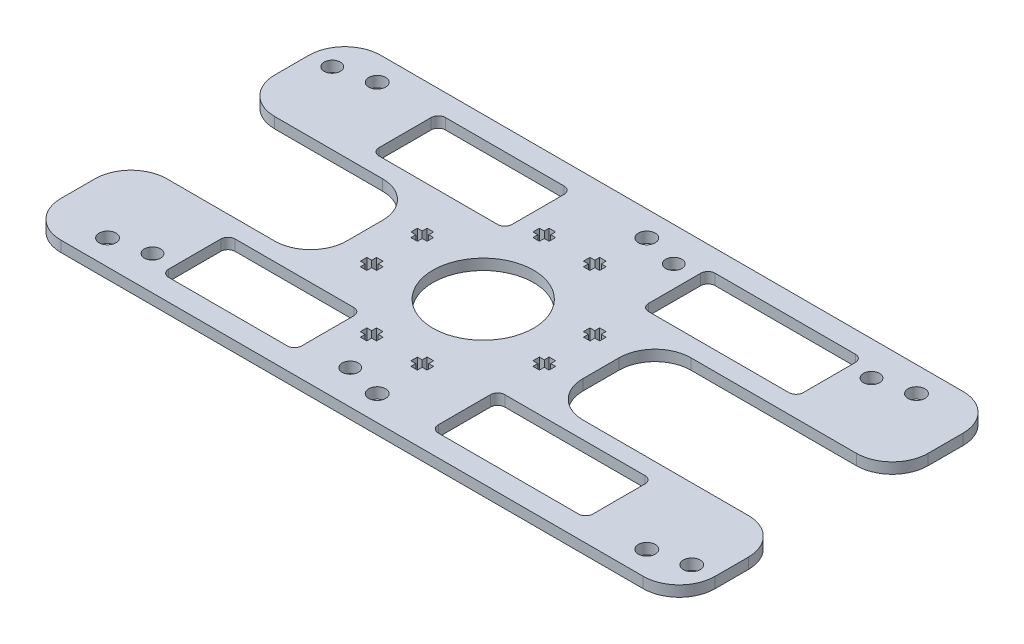
SolidWorks part; units mm, degrees
ref_plane "Front Plane" through (0, 0, 0) normal (0, 0, 1) x (1, 0, 0)
ref_plane "Top Plane" through (0, 0, 0) normal (0, 1, 0) x (1, 0, 0)
ref_plane "Right Plane" through (0, 0, 0) normal (1, 0, 0) x (0, 0, -1)
sketch "Sketch1" plane through (0, 0, 0) normal (0, 1, 0) x (1, 0, 0)
  line L2 (24.6852, -44.2664) -> (93.3361, -44.2664)
  line L4 (93.3361, 44.7336) -> (24.6837, 44.7336)
  line L7 (24.6837, 44.7336) -> (-88.6639, 44.7336)
  line L8 (-88.6639, 44.7336) -> (-88.6639, 15.2336)
  line L9 (-88.6639, -44.2664) -> (24.6852, -44.2664)
  line L17 (93.3361, -44.2664) -> (93.3361, -15)
  line L18 (-88.6639, 15.2336) -> (-38.6639, 15.2336)
  line L19 (-38.6639, 15.2336) -> (-38.6639, -14.7664)
  line L20 (-38.6639, -14.7664) -> (-88.6639, -14.7664)
  line L23 (93.3361, 15) -> (27.3361, 15)
  line L24 (27.3361, 15) -> (27.3361, -15)
  line L25 (27.3361, -15) -> (93.3361, -15)
  line L26 (-88.6639, -14.7664) -> (-88.6639, -44.2664)
  line L27 (93.3361, 15) -> (93.3361, 44.7336)
  circle A10 centre (-5.6639, 0.2336) radius 14
  circle A19 centre (-72.6639, -37.2664) radius 2.35
  circle A22 centre (2.3361, -37.2664) radius 2.35
  circle A25 centre (77.3361, -37.2664) radius 2.35
  circle A28 centre (77.3361, 37.7336) radius 2.35
  circle A31 centre (2.3361, 37.7336) radius 2.35
  circle A34 centre (-72.6639, 37.7336) radius 2.35
  point P7 (27.3361, 0)
  point P10 (-38.6639, 0.2336)
  dimension "D2" = 89
  dimension "D3" = 30
  dimension "D5" = 4.7
  dimension "D4" = 50
  dimension "D6" = 89
  dimension "D7" = 7
  dimension "D8" = 7
  dimension "D9" = 7
  dimension "D10" = 75
  dimension "D11" = 75
  dimension "D12" = 37.5
  dimension "D13" = 8
  dimension "D14" = 33
  dimension "D15" = 182
extrude "Boss-Extrude1" add sketch "Sketch1" along normal blind 3
sketch "Sketch2" plane through (0, 0, 0) normal (0, 1, 0) x (1, 0, 0)
  line L0 (0, 0) -> (-142.7211, 0) construction
ref_axis "Axis1" through (-5.6639, 0, -0.2336) along (0, 1, 0)
sketch "Sketch3" plane through (0, 3, 0) normal (0, 1, 0) x (1, 0, 0)
  line L12 (20.5861, -7.6958) -> (20.5861, -5.8958)
  line L13 (20.5861, -5.8958) -> (19.2361, -5.8958)
  line L14 (19.2361, -5.8958) -> (19.2361, -4.5458)
  line L15 (19.2361, -4.5458) -> (17.4361, -4.5458)
  line L16 (17.4361, -4.5458) -> (17.4361, -5.8958)
  line L17 (17.4361, -5.8958) -> (16.0861, -5.8958)
  line L18 (16.0861, -5.8958) -> (16.0861, -7.6958)
  line L19 (16.0861, -7.6958) -> (17.4361, -7.6958)
  line L20 (17.4361, -7.6958) -> (17.4361, -9.0458)
  line L21 (17.4361, -9.0458) -> (19.2361, -9.0458)
  line L22 (19.2361, -9.0458) -> (19.2361, -7.6958)
  line L23 (19.2361, -7.6958) -> (20.5861, -7.6958)
  line L24 (20.5861, -7.6958) -> (20.5861, -5.8958)
  line L25 (20.5861, -5.8958) -> (19.2361, -5.8958)
  line L26 (19.2361, -5.8958) -> (19.2361, -4.5458)
  line L27 (19.2361, -4.5458) -> (17.4361, -4.5458)
  line L28 (17.4361, -4.5458) -> (17.4361, -5.8958)
  line L29 (17.4361, -5.8958) -> (16.0861, -5.8958)
  line L30 (16.0861, -5.8958) -> (16.0861, -7.6958)
  line L31 (16.0861, -7.6958) -> (17.4361, -7.6958)
  line L32 (17.4361, -7.6958) -> (17.4361, -9.0458)
  line L33 (17.4361, -9.0458) -> (19.2361, -9.0458)
  line L34 (19.2361, -9.0458) -> (19.2361, -7.6958)
  line L35 (19.2361, -7.6958) -> (20.5861, -7.6958)
  line L36 (17.4361, 5.013) -> (19.2361, 5.013)
  line L37 (19.2361, 5.013) -> (19.2361, 6.363)
  line L38 (19.2361, 6.363) -> (20.5861, 6.363)
  line L39 (20.5861, 6.363) -> (20.5861, 8.163)
  line L40 (20.5861, 8.163) -> (19.2361, 8.163)
  line L41 (19.2361, 8.163) -> (19.2361, 9.513)
  line L42 (19.2361, 9.513) -> (17.4361, 9.513)
  line L43 (17.4361, 9.513) -> (17.4361, 8.163)
  line L44 (17.4361, 8.163) -> (16.0861, 8.163)
  line L45 (16.0861, 8.163) -> (16.0861, 6.363)
  line L46 (16.0861, 6.363) -> (17.4361, 6.363)
  line L47 (17.4361, 6.363) -> (17.4361, 5.013)
  line L48 (17.4361, 5.013) -> (19.2361, 5.013)
  line L49 (19.2361, 5.013) -> (19.2361, 6.363)
  line L50 (19.2361, 6.363) -> (20.5861, 6.363)
  line L51 (20.5861, 6.363) -> (20.5861, 8.163)
  line L52 (20.5861, 8.163) -> (19.2361, 8.163)
  line L53 (19.2361, 8.163) -> (19.2361, 9.513)
  line L54 (19.2361, 9.513) -> (17.4361, 9.513)
  line L55 (17.4361, 9.513) -> (17.4361, 8.163)
  line L56 (17.4361, 8.163) -> (16.0861, 8.163)
  line L57 (16.0861, 8.163) -> (16.0861, 6.363)
  line L58 (16.0861, 6.363) -> (17.4361, 6.363)
  line L59 (17.4361, 6.363) -> (17.4361, 5.013)
  line L60 (-13.5934, -22.8664) -> (-14.9434, -22.8664)
  line L61 (-14.9434, -22.8664) -> (-14.9434, -24.6664)
  line L62 (-14.9434, -24.6664) -> (-13.5934, -24.6664)
  line L63 (-13.5934, -24.6664) -> (-13.5934, -26.0164)
  line L64 (-13.5934, -26.0164) -> (-11.7934, -26.0164)
  line L65 (-11.7934, -26.0164) -> (-11.7934, -24.6664)
  line L66 (-11.7934, -24.6664) -> (-10.4434, -24.6664)
  line L67 (-10.4434, -24.6664) -> (-10.4434, -22.8664)
  line L68 (-10.4434, -22.8664) -> (-11.7934, -22.8664)
  line L69 (-11.7934, -22.8664) -> (-11.7934, -21.5164)
  line L70 (-11.7934, -21.5164) -> (-13.5934, -21.5164)
  line L71 (-13.5934, -21.5164) -> (-13.5934, -22.8664)
  line L72 (-13.5934, -22.8664) -> (-14.9434, -22.8664)
  line L73 (-14.9434, -22.8664) -> (-14.9434, -24.6664)
  line L74 (-14.9434, -24.6664) -> (-13.5934, -24.6664)
  line L75 (-13.5934, -24.6664) -> (-13.5934, -26.0164)
  line L76 (-13.5934, -26.0164) -> (-11.7934, -26.0164)
  line L77 (-11.7934, -26.0164) -> (-11.7934, -24.6664)
  line L78 (-11.7934, -24.6664) -> (-10.4434, -24.6664)
  line L79 (-10.4434, -24.6664) -> (-10.4434, -22.8664)
  line L80 (-10.4434, -22.8664) -> (-11.7934, -22.8664)
  line L81 (-11.7934, -22.8664) -> (-11.7934, -21.5164)
  line L82 (-11.7934, -21.5164) -> (-13.5934, -21.5164)
  line L83 (-13.5934, -21.5164) -> (-13.5934, -22.8664)
  line L84 (-31.9139, 8.163) -> (-31.9139, 6.363)
  line L85 (-31.9139, 6.363) -> (-30.5639, 6.363)
  line L86 (-30.5639, 6.363) -> (-30.5639, 5.013)
  line L87 (-30.5639, 5.013) -> (-28.7639, 5.013)
  line L88 (-28.7639, 5.013) -> (-28.7639, 6.363)
  line L89 (-28.7639, 6.363) -> (-27.4139, 6.363)
  line L90 (-27.4139, 6.363) -> (-27.4139, 8.163)
  line L91 (-27.4139, 8.163) -> (-28.7639, 8.163)
  line L92 (-28.7639, 8.163) -> (-28.7639, 9.513)
  line L93 (-28.7639, 9.513) -> (-30.5639, 9.513)
  line L94 (-30.5639, 9.513) -> (-30.5639, 8.163)
  line L95 (-30.5639, 8.163) -> (-31.9139, 8.163)
  line L96 (-31.9139, 8.163) -> (-31.9139, 6.363)
  line L97 (-31.9139, 6.363) -> (-30.5639, 6.363)
  line L98 (-30.5639, 6.363) -> (-30.5639, 5.013)
  line L99 (-30.5639, 5.013) -> (-28.7639, 5.013)
  line L100 (-28.7639, 5.013) -> (-28.7639, 6.363)
  line L101 (-28.7639, 6.363) -> (-27.4139, 6.363)
  line L102 (-27.4139, 6.363) -> (-27.4139, 8.163)
  line L103 (-27.4139, 8.163) -> (-28.7639, 8.163)
  line L104 (-28.7639, 8.163) -> (-28.7639, 9.513)
  line L105 (-28.7639, 9.513) -> (-30.5639, 9.513)
  line L106 (-30.5639, 9.513) -> (-30.5639, 8.163)
  line L107 (-30.5639, 8.163) -> (-31.9139, 8.163)
  line L108 (-0.8845, -24.6664) -> (0.4655, -24.6664)
  line L109 (0.4655, -24.6664) -> (0.4655, -26.0164)
  line L110 (0.4655, -26.0164) -> (2.2655, -26.0164)
  line L111 (2.2655, -26.0164) -> (2.2655, -24.6664)
  line L112 (2.2655, -24.6664) -> (3.6155, -24.6664)
  line L113 (3.6155, -24.6664) -> (3.6155, -22.8664)
  line L114 (3.6155, -22.8664) -> (2.2655, -22.8664)
  line L115 (2.2655, -22.8664) -> (2.2655, -21.5164)
  line L116 (2.2655, -21.5164) -> (0.4655, -21.5164)
  line L117 (0.4655, -21.5164) -> (0.4655, -22.8664)
  line L118 (0.4655, -22.8664) -> (-0.8845, -22.8664)
  line L119 (-0.8845, -22.8664) -> (-0.8845, -24.6664)
  line L120 (-0.8845, -24.6664) -> (0.4655, -24.6664)
  line L121 (0.4655, -24.6664) -> (0.4655, -26.0164)
  line L122 (0.4655, -26.0164) -> (2.2655, -26.0164)
  line L123 (2.2655, -26.0164) -> (2.2655, -24.6664)
  line L124 (2.2655, -24.6664) -> (3.6155, -24.6664)
  line L125 (3.6155, -24.6664) -> (3.6155, -22.8664)
  line L126 (3.6155, -22.8664) -> (2.2655, -22.8664)
  line L127 (2.2655, -22.8664) -> (2.2655, -21.5164)
  line L128 (2.2655, -21.5164) -> (0.4655, -21.5164)
  line L129 (0.4655, -21.5164) -> (0.4655, -22.8664)
  line L130 (0.4655, -22.8664) -> (-0.8845, -22.8664)
  line L131 (-0.8845, -22.8664) -> (-0.8845, -24.6664)
  line L132 (-31.9139, -7.6958) -> (-30.5639, -7.6958)
  line L133 (-31.9139, -5.8958) -> (-31.9139, -7.6958)
  line L134 (-30.5639, -5.8958) -> (-31.9139, -5.8958)
  line L135 (-30.5639, -4.5458) -> (-30.5639, -5.8958)
  line L136 (-28.7639, -4.5458) -> (-30.5639, -4.5458)
  line L137 (-28.7639, -5.8958) -> (-28.7639, -4.5458)
  line L138 (-27.4139, -5.8958) -> (-28.7639, -5.8958)
  line L139 (-27.4139, -7.6958) -> (-27.4139, -5.8958)
  line L140 (-28.7639, -7.6958) -> (-27.4139, -7.6958)
  line L141 (-28.7639, -9.0458) -> (-28.7639, -7.6958)
  line L142 (-30.5639, -9.0458) -> (-28.7639, -9.0458)
  line L143 (-30.5639, -7.6958) -> (-30.5639, -9.0458)
  line L144 (-31.9139, -7.6958) -> (-30.5639, -7.6958)
  line L145 (-31.9139, -5.8958) -> (-31.9139, -7.6958)
  line L146 (-30.5639, -5.8958) -> (-31.9139, -5.8958)
  line L147 (-30.5639, -4.5458) -> (-30.5639, -5.8958)
  line L148 (-28.7639, -4.5458) -> (-30.5639, -4.5458)
  line L149 (-28.7639, -5.8958) -> (-28.7639, -4.5458)
  line L150 (-27.4139, -5.8958) -> (-28.7639, -5.8958)
  line L151 (-27.4139, -7.6958) -> (-27.4139, -5.8958)
  line L152 (-28.7639, -7.6958) -> (-27.4139, -7.6958)
  line L153 (-28.7639, -9.0458) -> (-28.7639, -7.6958)
  line L154 (-30.5639, -9.0458) -> (-28.7639, -9.0458)
  line L155 (-30.5639, -7.6958) -> (-30.5639, -9.0458)
  line L156 (0.4655, 26.4836) -> (0.4655, 25.1336)
  line L157 (0.4655, 25.1336) -> (-0.8845, 25.1336)
  line L158 (-0.8845, 25.1336) -> (-0.8845, 23.3336)
  line L159 (-0.8845, 23.3336) -> (0.4655, 23.3336)
  line L160 (0.4655, 23.3336) -> (0.4655, 21.9836)
  line L161 (0.4655, 21.9836) -> (2.2655, 21.9836)
  line L162 (2.2655, 21.9836) -> (2.2655, 23.3336)
  line L163 (2.2655, 23.3336) -> (3.6155, 23.3336)
  line L164 (3.6155, 23.3336) -> (3.6155, 25.1336)
  line L165 (3.6155, 25.1336) -> (2.2655, 25.1336)
  line L166 (2.2655, 25.1336) -> (2.2655, 26.4836)
  line L167 (2.2655, 26.4836) -> (0.4655, 26.4836)
  line L168 (0.4655, 26.4836) -> (0.4655, 25.1336)
  line L169 (0.4655, 25.1336) -> (-0.8845, 25.1336)
  line L170 (-0.8845, 25.1336) -> (-0.8845, 23.3336)
  line L171 (-0.8845, 23.3336) -> (0.4655, 23.3336)
  line L172 (0.4655, 23.3336) -> (0.4655, 21.9836)
  line L173 (0.4655, 21.9836) -> (2.2655, 21.9836)
  line L174 (2.2655, 21.9836) -> (2.2655, 23.3336)
  line L175 (2.2655, 23.3336) -> (3.6155, 23.3336)
  line L176 (3.6155, 23.3336) -> (3.6155, 25.1336)
  line L177 (3.6155, 25.1336) -> (2.2655, 25.1336)
  line L178 (2.2655, 25.1336) -> (2.2655, 26.4836)
  line L179 (2.2655, 26.4836) -> (0.4655, 26.4836)
  line L180 (-13.5934, 26.4836) -> (-13.5934, 25.1336)
  line L181 (-13.5934, 25.1336) -> (-14.9434, 25.1336)
  line L182 (-14.9434, 25.1336) -> (-14.9434, 23.3336)
  line L183 (-14.9434, 23.3336) -> (-13.5934, 23.3336)
  line L184 (-13.5934, 23.3336) -> (-13.5934, 21.9836)
  line L185 (-13.5934, 21.9836) -> (-11.7934, 21.9836)
  line L186 (-11.7934, 21.9836) -> (-11.7934, 23.3336)
  line L187 (-11.7934, 23.3336) -> (-10.4434, 23.3336)
  line L188 (-10.4434, 23.3336) -> (-10.4434, 25.1336)
  line L189 (-10.4434, 25.1336) -> (-11.7934, 25.1336)
  line L190 (-11.7934, 25.1336) -> (-11.7934, 26.4836)
  line L191 (-11.7934, 26.4836) -> (-13.5934, 26.4836)
  line L192 (-13.5934, 26.4836) -> (-13.5934, 25.1336)
  line L193 (-13.5934, 25.1336) -> (-14.9434, 25.1336)
  line L194 (-14.9434, 25.1336) -> (-14.9434, 23.3336)
  line L195 (-14.9434, 23.3336) -> (-13.5934, 23.3336)
  line L196 (-13.5934, 23.3336) -> (-13.5934, 21.9836)
  line L197 (-13.5934, 21.9836) -> (-11.7934, 21.9836)
  line L198 (-11.7934, 21.9836) -> (-11.7934, 23.3336)
  line L199 (-11.7934, 23.3336) -> (-10.4434, 23.3336)
  line L200 (-10.4434, 23.3336) -> (-10.4434, 25.1336)
  line L201 (-10.4434, 25.1336) -> (-11.7934, 25.1336)
  line L202 (-11.7934, 25.1336) -> (-11.7934, 26.4836)
  line L203 (-11.7934, 26.4836) -> (-13.5934, 26.4836)
  dimension "D1" = 0
  dimension "D2" = 0
  dimension "D3" = 0
  dimension "D4" = 0
  dimension "D5" = 0
  dimension "D6" = 0
  dimension "D7" = 0
  dimension "D8" = 0
extrude "Cut-Extrude1" cut sketch "Sketch3" against normal through all
fillet "Fillet1" radius 10 12 edges at (27.3361, 1.5, 15) (27.3361, 1.5, -15) (93.3361, 1.5, 44.2664) (93.3361, 1.5, 15) (93.3361, 1.5, -15) (93.3361, 1.5, -44.7336) (-88.6639, 1.5, 44.2664) (-88.6639, 1.5, 14.7664) (-38.6639, 1.5, 14.7664) (-38.6639, 1.5, -15.2336) (-88.6639, 1.5, -15.2336) (-88.6639, 1.5, -44.7336)
sketch "Sketch4" plane through (0, 3, 0) normal (0, 1, 0) x (1, 0, 0)
  circle A0 centre (87.3361, -34.7664) radius 2.35 construction
  circle A1 centre (87.3361, -34.7664) radius 2.35
  circle A2 centre (67.3361, 35.2336) radius 2.25 construction
  circle A3 centre (67.3361, 35.2336) radius 2.25
  circle A4 centre (12.3361, 35.2336) radius 2.25 construction
  circle A5 centre (12.3361, 35.2336) radius 2.25
  circle A6 centre (-82.6639, 35.2336) radius 2.25 construction
  circle A7 centre (-82.6639, 35.2336) radius 2.25
  circle A8 centre (-62.6639, -34.7664) radius 2.25 construction
  circle A9 centre (-62.6639, -34.7664) radius 2.25
  circle A10 centre (-7.6639, -34.7664) radius 2.25 construction
  circle A11 centre (-7.6639, -34.7664) radius 2.25
extrude "Cut-Extrude2" cut sketch "Sketch4" against normal blind 10
sketch "Sketch5" plane through (0, 3, 0) normal (0, 1, 0) x (1, 0, 0)
  line L4 (59.3361, -19.7664) -> (20.3361, -19.7664)
  line L5 (61.3361, -36.2664) -> (61.3361, -21.7664)
  line L6 (20.3361, -38.2664) -> (59.3361, -38.2664)
  line L7 (18.3361, -21.7664) -> (18.3361, -36.2664)
  line L8 (59.3361, -19.7664) -> (20.3361, -19.7664)
  line L9 (61.3361, -36.2664) -> (61.3361, -21.7664)
  line L10 (20.3361, -38.2664) -> (59.3361, -38.2664)
  line L11 (18.3361, -21.7664) -> (18.3361, -36.2664)
  line L12 (18.3361, 36.7336) -> (18.3361, 22.2336)
  line L13 (59.3361, 38.7336) -> (20.3361, 38.7336)
  line L14 (61.3361, 22.2336) -> (61.3361, 36.7336)
  line L15 (20.3361, 20.2336) -> (59.3361, 20.2336)
  line L16 (18.3361, 36.7336) -> (18.3361, 22.2336)
  line L17 (59.3361, 38.7336) -> (20.3361, 38.7336)
  line L18 (61.3361, 22.2336) -> (61.3361, 36.7336)
  line L19 (20.3361, 20.2336) -> (59.3361, 20.2336)
  line L20 (-56.6639, -21.7664) -> (-56.6639, -36.2664)
  line L21 (-21.6639, -19.7664) -> (-54.6639, -19.7664)
  line L22 (-19.6639, -36.2664) -> (-19.6639, -21.7664)
  line L23 (-54.6639, -38.2664) -> (-21.6639, -38.2664)
  line L24 (-56.6639, -21.7664) -> (-56.6639, -36.2664)
  line L25 (-21.6639, -19.7664) -> (-54.6639, -19.7664)
  line L26 (-19.6639, -36.2664) -> (-19.6639, -21.7664)
  line L27 (-54.6639, -38.2664) -> (-21.6639, -38.2664)
  line L28 (-56.6639, 36.7336) -> (-56.6639, 22.2336)
  line L29 (-21.6639, 38.7336) -> (-54.6639, 38.7336)
  line L30 (-19.6639, 22.2336) -> (-19.6639, 36.7336)
  line L31 (-54.6639, 20.2336) -> (-21.6639, 20.2336)
  line L32 (-56.6639, 36.7336) -> (-56.6639, 22.2336)
  line L33 (-21.6639, 38.7336) -> (-54.6639, 38.7336)
  line L34 (-19.6639, 22.2336) -> (-19.6639, 36.7336)
  line L35 (-54.6639, 20.2336) -> (-21.6639, 20.2336)
  arc A4 (61.3361, -21.7664) -> (59.3361, -19.7664) centre (59.3361, -21.7664) ccw
  arc A5 (59.3361, -38.2664) -> (61.3361, -36.2664) centre (59.3361, -36.2664) ccw
  arc A6 (18.3361, -36.2664) -> (20.3361, -38.2664) centre (20.3361, -36.2664) ccw
  arc A7 (20.3361, -19.7664) -> (18.3361, -21.7664) centre (20.3361, -21.7664) ccw
  arc A8 (61.3361, -21.7664) -> (59.3361, -19.7664) centre (59.3361, -21.7664) ccw
  arc A9 (59.3361, -38.2664) -> (61.3361, -36.2664) centre (59.3361, -36.2664) ccw
  arc A10 (18.3361, -36.2664) -> (20.3361, -38.2664) centre (20.3361, -36.2664) ccw
  arc A11 (20.3361, -19.7664) -> (18.3361, -21.7664) centre (20.3361, -21.7664) ccw
  arc A12 (20.3361, 38.7336) -> (18.3361, 36.7336) centre (20.3361, 36.7336) ccw
  arc A13 (61.3361, 36.7336) -> (59.3361, 38.7336) centre (59.3361, 36.7336) ccw
  arc A14 (59.3361, 20.2336) -> (61.3361, 22.2336) centre (59.3361, 22.2336) ccw
  arc A15 (18.3361, 22.2336) -> (20.3361, 20.2336) centre (20.3361, 22.2336) ccw
  arc A16 (20.3361, 38.7336) -> (18.3361, 36.7336) centre (20.3361, 36.7336) ccw
  arc A17 (61.3361, 36.7336) -> (59.3361, 38.7336) centre (59.3361, 36.7336) ccw
  arc A18 (59.3361, 20.2336) -> (61.3361, 22.2336) centre (59.3361, 22.2336) ccw
  arc A19 (18.3361, 22.2336) -> (20.3361, 20.2336) centre (20.3361, 22.2336) ccw
  arc A20 (-54.6639, -19.7664) -> (-56.6639, -21.7664) centre (-54.6639, -21.7664) ccw
  arc A21 (-19.6639, -21.7664) -> (-21.6639, -19.7664) centre (-21.6639, -21.7664) ccw
  arc A22 (-21.6639, -38.2664) -> (-19.6639, -36.2664) centre (-21.6639, -36.2664) ccw
  arc A23 (-56.6639, -36.2664) -> (-54.6639, -38.2664) centre (-54.6639, -36.2664) ccw
  arc A24 (-54.6639, -19.7664) -> (-56.6639, -21.7664) centre (-54.6639, -21.7664) ccw
  arc A25 (-19.6639, -21.7664) -> (-21.6639, -19.7664) centre (-21.6639, -21.7664) ccw
  arc A26 (-21.6639, -38.2664) -> (-19.6639, -36.2664) centre (-21.6639, -36.2664) ccw
  arc A27 (-56.6639, -36.2664) -> (-54.6639, -38.2664) centre (-54.6639, -36.2664) ccw
  arc A28 (-54.6639, 38.7336) -> (-56.6639, 36.7336) centre (-54.6639, 36.7336) ccw
  arc A29 (-19.6639, 36.7336) -> (-21.6639, 38.7336) centre (-21.6639, 36.7336) ccw
  arc A30 (-21.6639, 20.2336) -> (-19.6639, 22.2336) centre (-21.6639, 22.2336) ccw
  arc A31 (-56.6639, 22.2336) -> (-54.6639, 20.2336) centre (-54.6639, 22.2336) ccw
  arc A32 (-54.6639, 38.7336) -> (-56.6639, 36.7336) centre (-54.6639, 36.7336) ccw
  arc A33 (-19.6639, 36.7336) -> (-21.6639, 38.7336) centre (-21.6639, 36.7336) ccw
  arc A34 (-21.6639, 20.2336) -> (-19.6639, 22.2336) centre (-21.6639, 22.2336) ccw
  arc A35 (-56.6639, 22.2336) -> (-54.6639, 20.2336) centre (-54.6639, 22.2336) ccw
  dimension "D1" = 0
  dimension "D2" = 0
  dimension "D3" = 0
  dimension "D4" = 0
extrude "Cut-Extrude3" cut sketch "Sketch5" against normal blind 10
sketch "Sketch6" plane through (0, 3, 0) normal (0, 1, 0) x (1, 0, 0)
  line L4 (-54.6639, 20.2336) -> (-21.6639, 20.2336)
  line L5 (-56.6639, 36.7336) -> (-56.6639, 22.2336)
  line L6 (-21.6639, 38.7336) -> (-54.6639, 38.7336)
  line L7 (-19.6639, 22.2336) -> (-19.6639, 36.7336)
  line L8 (-54.6639, 20.2336) -> (-21.6639, 20.2336)
  line L9 (-56.6639, 36.7336) -> (-56.6639, 22.2336)
  line L10 (-21.6639, 38.7336) -> (-54.6639, 38.7336)
  line L11 (-19.6639, 22.2336) -> (-19.6639, 36.7336)
  line L12 (20.3361, 20.2336) -> (59.3361, 20.2336)
  line L13 (18.3361, 36.7336) -> (18.3361, 22.2336)
  line L14 (59.3361, 38.7336) -> (20.3361, 38.7336)
  line L15 (61.3361, 22.2336) -> (61.3361, 36.7336)
  line L16 (20.3361, 20.2336) -> (59.3361, 20.2336)
  line L17 (18.3361, 36.7336) -> (18.3361, 22.2336)
  line L18 (59.3361, 38.7336) -> (20.3361, 38.7336)
  line L19 (61.3361, 22.2336) -> (61.3361, 36.7336)
  line L20 (-54.6639, -38.2664) -> (-21.6639, -38.2664)
  line L21 (-56.6639, -21.7664) -> (-56.6639, -36.2664)
  line L22 (-21.6639, -19.7664) -> (-54.6639, -19.7664)
  line L23 (-19.6639, -36.2664) -> (-19.6639, -21.7664)
  line L24 (-54.6639, -38.2664) -> (-21.6639, -38.2664)
  line L25 (-56.6639, -21.7664) -> (-56.6639, -36.2664)
  line L26 (-21.6639, -19.7664) -> (-54.6639, -19.7664)
  line L27 (-19.6639, -36.2664) -> (-19.6639, -21.7664)
  line L28 (18.3361, -21.7664) -> (18.3361, -36.2664)
  line L29 (59.3361, -19.7664) -> (20.3361, -19.7664)
  line L30 (61.3361, -36.2664) -> (61.3361, -21.7664)
  line L31 (20.3361, -38.2664) -> (59.3361, -38.2664)
  line L32 (18.3361, -21.7664) -> (18.3361, -36.2664)
  line L33 (59.3361, -19.7664) -> (20.3361, -19.7664)
  line L34 (61.3361, -36.2664) -> (61.3361, -21.7664)
  line L35 (20.3361, -38.2664) -> (59.3361, -38.2664)
  line L36 (20.5861, -7.6958) -> (20.5861, -5.8958)
  line L37 (19.2361, -7.6958) -> (20.5861, -7.6958)
  line L38 (19.2361, -9.0458) -> (19.2361, -7.6958)
  line L39 (17.4361, -9.0458) -> (19.2361, -9.0458)
  line L40 (17.4361, -7.6958) -> (17.4361, -9.0458)
  line L41 (16.0861, -7.6958) -> (17.4361, -7.6958)
  line L42 (16.0861, -5.8958) -> (16.0861, -7.6958)
  line L43 (17.4361, -5.8958) -> (16.0861, -5.8958)
  line L44 (17.4361, -4.5458) -> (17.4361, -5.8958)
  line L45 (19.2361, -4.5458) -> (17.4361, -4.5458)
  line L46 (19.2361, -5.8958) -> (19.2361, -4.5458)
  line L47 (20.5861, -5.8958) -> (19.2361, -5.8958)
  line L48 (20.5861, -7.6958) -> (20.5861, -5.8958)
  line L49 (19.2361, -7.6958) -> (20.5861, -7.6958)
  line L50 (19.2361, -9.0458) -> (19.2361, -7.6958)
  line L51 (17.4361, -9.0458) -> (19.2361, -9.0458)
  line L52 (17.4361, -7.6958) -> (17.4361, -9.0458)
  line L53 (16.0861, -7.6958) -> (17.4361, -7.6958)
  line L54 (16.0861, -5.8958) -> (16.0861, -7.6958)
  line L55 (17.4361, -5.8958) -> (16.0861, -5.8958)
  line L56 (17.4361, -4.5458) -> (17.4361, -5.8958)
  line L57 (19.2361, -4.5458) -> (17.4361, -4.5458)
  line L58 (19.2361, -5.8958) -> (19.2361, -4.5458)
  line L59 (20.5861, -5.8958) -> (19.2361, -5.8958)
  line L60 (-30.5639, -9.0458) -> (-28.7639, -9.0458)
  line L61 (-30.5639, -7.6958) -> (-30.5639, -9.0458)
  line L62 (-31.9139, -7.6958) -> (-30.5639, -7.6958)
  line L63 (-31.9139, -5.8958) -> (-31.9139, -7.6958)
  line L64 (-30.5639, -5.8958) -> (-31.9139, -5.8958)
  line L65 (-30.5639, -4.5458) -> (-30.5639, -5.8958)
  line L66 (-28.7639, -4.5458) -> (-30.5639, -4.5458)
  line L67 (-28.7639, -5.8958) -> (-28.7639, -4.5458)
  line L68 (-27.4139, -5.8958) -> (-28.7639, -5.8958)
  line L69 (-27.4139, -7.6958) -> (-27.4139, -5.8958)
  line L70 (-28.7639, -7.6958) -> (-27.4139, -7.6958)
  line L71 (-28.7639, -9.0458) -> (-28.7639, -7.6958)
  line L72 (-30.5639, -9.0458) -> (-28.7639, -9.0458)
  line L73 (-30.5639, -7.6958) -> (-30.5639, -9.0458)
  line L74 (-31.9139, -7.6958) -> (-30.5639, -7.6958)
  line L75 (-31.9139, -5.8958) -> (-31.9139, -7.6958)
  line L76 (-30.5639, -5.8958) -> (-31.9139, -5.8958)
  line L77 (-30.5639, -4.5458) -> (-30.5639, -5.8958)
  line L78 (-28.7639, -4.5458) -> (-30.5639, -4.5458)
  line L79 (-28.7639, -5.8958) -> (-28.7639, -4.5458)
  line L80 (-27.4139, -5.8958) -> (-28.7639, -5.8958)
  line L81 (-27.4139, -7.6958) -> (-27.4139, -5.8958)
  line L82 (-28.7639, -7.6958) -> (-27.4139, -7.6958)
  line L83 (-28.7639, -9.0458) -> (-28.7639, -7.6958)
  line L84 (0.4655, 26.4836) -> (0.4655, 25.1336)
  line L85 (2.2655, 26.4836) -> (0.4655, 26.4836)
  line L86 (2.2655, 25.1336) -> (2.2655, 26.4836)
  line L87 (3.6155, 25.1336) -> (2.2655, 25.1336)
  line L88 (3.6155, 23.3336) -> (3.6155, 25.1336)
  line L89 (2.2655, 23.3336) -> (3.6155, 23.3336)
  line L90 (2.2655, 21.9836) -> (2.2655, 23.3336)
  line L91 (0.4655, 21.9836) -> (2.2655, 21.9836)
  line L92 (0.4655, 23.3336) -> (0.4655, 21.9836)
  line L93 (-0.8845, 23.3336) -> (0.4655, 23.3336)
  line L94 (-0.8845, 25.1336) -> (-0.8845, 23.3336)
  line L95 (0.4655, 25.1336) -> (-0.8845, 25.1336)
  line L96 (0.4655, 26.4836) -> (0.4655, 25.1336)
  line L97 (2.2655, 26.4836) -> (0.4655, 26.4836)
  line L98 (2.2655, 25.1336) -> (2.2655, 26.4836)
  line L99 (3.6155, 25.1336) -> (2.2655, 25.1336)
  line L100 (3.6155, 23.3336) -> (3.6155, 25.1336)
  line L101 (2.2655, 23.3336) -> (3.6155, 23.3336)
  line L102 (2.2655, 21.9836) -> (2.2655, 23.3336)
  line L103 (0.4655, 21.9836) -> (2.2655, 21.9836)
  line L104 (0.4655, 23.3336) -> (0.4655, 21.9836)
  line L105 (-0.8845, 23.3336) -> (0.4655, 23.3336)
  line L106 (-0.8845, 25.1336) -> (-0.8845, 23.3336)
  line L107 (0.4655, 25.1336) -> (-0.8845, 25.1336)
  line L108 (-14.9434, 25.1336) -> (-14.9434, 23.3336)
  line L109 (-13.5934, 25.1336) -> (-14.9434, 25.1336)
  line L110 (-13.5934, 26.4836) -> (-13.5934, 25.1336)
  line L111 (-11.7934, 26.4836) -> (-13.5934, 26.4836)
  line L112 (-11.7934, 25.1336) -> (-11.7934, 26.4836)
  line L113 (-10.4434, 25.1336) -> (-11.7934, 25.1336)
  line L114 (-10.4434, 23.3336) -> (-10.4434, 25.1336)
  line L115 (-11.7934, 23.3336) -> (-10.4434, 23.3336)
  line L116 (-11.7934, 21.9836) -> (-11.7934, 23.3336)
  line L117 (-13.5934, 21.9836) -> (-11.7934, 21.9836)
  line L118 (-13.5934, 23.3336) -> (-13.5934, 21.9836)
  line L119 (-14.9434, 23.3336) -> (-13.5934, 23.3336)
  line L120 (-14.9434, 25.1336) -> (-14.9434, 23.3336)
  line L121 (-13.5934, 25.1336) -> (-14.9434, 25.1336)
  line L122 (-13.5934, 26.4836) -> (-13.5934, 25.1336)
  line L123 (-11.7934, 26.4836) -> (-13.5934, 26.4836)
  line L124 (-11.7934, 25.1336) -> (-11.7934, 26.4836)
  line L125 (-10.4434, 25.1336) -> (-11.7934, 25.1336)
  line L126 (-10.4434, 23.3336) -> (-10.4434, 25.1336)
  line L127 (-11.7934, 23.3336) -> (-10.4434, 23.3336)
  line L128 (-11.7934, 21.9836) -> (-11.7934, 23.3336)
  line L129 (-13.5934, 21.9836) -> (-11.7934, 21.9836)
  line L130 (-13.5934, 23.3336) -> (-13.5934, 21.9836)
  line L131 (-14.9434, 23.3336) -> (-13.5934, 23.3336)
  line L132 (19.2361, 6.363) -> (20.5861, 6.363)
  line L133 (19.2361, 5.013) -> (19.2361, 6.363)
  line L134 (17.4361, 5.013) -> (19.2361, 5.013)
  line L135 (17.4361, 6.363) -> (17.4361, 5.013)
  line L136 (16.0861, 6.363) -> (17.4361, 6.363)
  line L137 (16.0861, 8.163) -> (16.0861, 6.363)
  line L138 (17.4361, 8.163) -> (16.0861, 8.163)
  line L139 (17.4361, 9.513) -> (17.4361, 8.163)
  line L140 (19.2361, 9.513) -> (17.4361, 9.513)
  line L141 (19.2361, 8.163) -> (19.2361, 9.513)
  line L142 (20.5861, 8.163) -> (19.2361, 8.163)
  line L143 (20.5861, 6.363) -> (20.5861, 8.163)
  line L144 (19.2361, 6.363) -> (20.5861, 6.363)
  line L145 (19.2361, 5.013) -> (19.2361, 6.363)
  line L146 (17.4361, 5.013) -> (19.2361, 5.013)
  line L147 (17.4361, 6.363) -> (17.4361, 5.013)
  line L148 (16.0861, 6.363) -> (17.4361, 6.363)
  line L149 (16.0861, 8.163) -> (16.0861, 6.363)
  line L150 (17.4361, 8.163) -> (16.0861, 8.163)
  line L151 (17.4361, 9.513) -> (17.4361, 8.163)
  line L152 (19.2361, 9.513) -> (17.4361, 9.513)
  line L153 (19.2361, 8.163) -> (19.2361, 9.513)
  line L154 (20.5861, 8.163) -> (19.2361, 8.163)
  line L155 (20.5861, 6.363) -> (20.5861, 8.163)
  line L156 (-31.9139, 8.163) -> (-31.9139, 6.363)
  line L157 (-30.5639, 8.163) -> (-31.9139, 8.163)
  line L158 (-30.5639, 9.513) -> (-30.5639, 8.163)
  line L159 (-28.7639, 9.513) -> (-30.5639, 9.513)
  line L160 (-28.7639, 8.163) -> (-28.7639, 9.513)
  line L161 (-27.4139, 8.163) -> (-28.7639, 8.163)
  line L162 (-27.4139, 6.363) -> (-27.4139, 8.163)
  line L163 (-28.7639, 6.363) -> (-27.4139, 6.363)
  line L164 (-28.7639, 5.013) -> (-28.7639, 6.363)
  line L165 (-30.5639, 5.013) -> (-28.7639, 5.013)
  line L166 (-30.5639, 6.363) -> (-30.5639, 5.013)
  line L167 (-31.9139, 6.363) -> (-30.5639, 6.363)
  line L168 (-31.9139, 8.163) -> (-31.9139, 6.363)
  line L169 (-30.5639, 8.163) -> (-31.9139, 8.163)
  line L170 (-30.5639, 9.513) -> (-30.5639, 8.163)
  line L171 (-28.7639, 9.513) -> (-30.5639, 9.513)
  line L172 (-28.7639, 8.163) -> (-28.7639, 9.513)
  line L173 (-27.4139, 8.163) -> (-28.7639, 8.163)
  line L174 (-27.4139, 6.363) -> (-27.4139, 8.163)
  line L175 (-28.7639, 6.363) -> (-27.4139, 6.363)
  line L176 (-28.7639, 5.013) -> (-28.7639, 6.363)
  line L177 (-30.5639, 5.013) -> (-28.7639, 5.013)
  line L178 (-30.5639, 6.363) -> (-30.5639, 5.013)
  line L179 (-31.9139, 6.363) -> (-30.5639, 6.363)
  line L180 (0.4655, -26.0164) -> (2.2655, -26.0164)
  line L181 (0.4655, -24.6664) -> (0.4655, -26.0164)
  line L182 (-0.8845, -24.6664) -> (0.4655, -24.6664)
  line L183 (-0.8845, -22.8664) -> (-0.8845, -24.6664)
  line L184 (0.4655, -22.8664) -> (-0.8845, -22.8664)
  line L185 (0.4655, -21.5164) -> (0.4655, -22.8664)
  line L186 (2.2655, -21.5164) -> (0.4655, -21.5164)
  line L187 (2.2655, -22.8664) -> (2.2655, -21.5164)
  line L188 (3.6155, -22.8664) -> (2.2655, -22.8664)
  line L189 (3.6155, -24.6664) -> (3.6155, -22.8664)
  line L190 (2.2655, -24.6664) -> (3.6155, -24.6664)
  line L191 (2.2655, -26.0164) -> (2.2655, -24.6664)
  line L192 (0.4655, -26.0164) -> (2.2655, -26.0164)
  line L193 (0.4655, -24.6664) -> (0.4655, -26.0164)
  line L194 (-0.8845, -24.6664) -> (0.4655, -24.6664)
  line L195 (-0.8845, -22.8664) -> (-0.8845, -24.6664)
  line L196 (0.4655, -22.8664) -> (-0.8845, -22.8664)
  line L197 (0.4655, -21.5164) -> (0.4655, -22.8664)
  line L198 (2.2655, -21.5164) -> (0.4655, -21.5164)
  line L199 (2.2655, -22.8664) -> (2.2655, -21.5164)
  line L200 (3.6155, -22.8664) -> (2.2655, -22.8664)
  line L201 (3.6155, -24.6664) -> (3.6155, -22.8664)
  line L202 (2.2655, -24.6664) -> (3.6155, -24.6664)
  line L203 (2.2655, -26.0164) -> (2.2655, -24.6664)
  line L212 (-13.5934, -22.8664) -> (-14.9434, -22.8664)
  line L213 (-13.5934, -21.5164) -> (-13.5934, -22.8664)
  line L214 (-11.7934, -21.5164) -> (-13.5934, -21.5164)
  line L215 (-11.7934, -22.8664) -> (-11.7934, -21.5164)
  line L216 (-10.4434, -22.8664) -> (-11.7934, -22.8664)
  line L217 (-10.4434, -24.6664) -> (-10.4434, -22.8664)
  line L218 (-11.7934, -24.6664) -> (-10.4434, -24.6664)
  line L219 (-11.7934, -26.0164) -> (-11.7934, -24.6664)
  line L220 (-13.5934, -26.0164) -> (-11.7934, -26.0164)
  line L221 (-13.5934, -24.6664) -> (-13.5934, -26.0164)
  line L222 (-14.9434, -24.6664) -> (-13.5934, -24.6664)
  line L223 (-14.9434, -22.8664) -> (-14.9434, -24.6664)
  line L224 (-13.5934, -22.8664) -> (-14.9434, -22.8664)
  line L225 (-13.5934, -21.5164) -> (-13.5934, -22.8664)
  line L226 (-11.7934, -21.5164) -> (-13.5934, -21.5164)
  line L227 (-11.7934, -22.8664) -> (-11.7934, -21.5164)
  line L228 (-10.4434, -22.8664) -> (-11.7934, -22.8664)
  line L229 (-10.4434, -24.6664) -> (-10.4434, -22.8664)
  line L230 (-11.7934, -24.6664) -> (-10.4434, -24.6664)
  line L231 (-11.7934, -26.0164) -> (-11.7934, -24.6664)
  line L232 (-13.5934, -26.0164) -> (-11.7934, -26.0164)
  line L233 (-13.5934, -24.6664) -> (-13.5934, -26.0164)
  line L234 (-14.9434, -24.6664) -> (-13.5934, -24.6664)
  line L235 (-14.9434, -22.8664) -> (-14.9434, -24.6664)
  line L236 (-78.6639, -44.2664) -> (83.3361, -44.2664)
  line L237 (93.3361, -34.2664) -> (93.3361, -25)
  line L238 (83.3361, -15) -> (37.3361, -15)
  line L239 (27.3361, -5) -> (27.3361, 5)
  line L240 (37.3361, 15) -> (83.3361, 15)
  line L241 (93.3361, 25) -> (93.3361, 34.7336)
  line L242 (83.3361, 44.7336) -> (-78.6639, 44.7336)
  line L243 (-88.6639, 34.7336) -> (-88.6639, 25.2336)
  line L244 (-78.6639, 15.2336) -> (-48.6639, 15.2336)
  line L245 (-38.6639, 5.2336) -> (-38.6639, -4.7664)
  line L246 (-48.6639, -14.7664) -> (-78.6639, -14.7664)
  line L247 (-88.6639, -24.7664) -> (-88.6639, -34.2664)
  line L248 (-78.6639, -44.2664) -> (83.3361, -44.2664)
  line L249 (93.3361, -34.2664) -> (93.3361, -25)
  line L250 (83.3361, -15) -> (37.3361, -15)
  line L251 (27.3361, -5) -> (27.3361, 5)
  line L252 (37.3361, 15) -> (83.3361, 15)
  line L253 (93.3361, 25) -> (93.3361, 34.7336)
  line L254 (83.3361, 44.7336) -> (-78.6639, 44.7336)
  line L255 (-88.6639, 34.7336) -> (-88.6639, 25.2336)
  line L256 (-78.6639, 15.2336) -> (-48.6639, 15.2336)
  line L257 (-38.6639, 5.2336) -> (-38.6639, -4.7664)
  line L258 (-48.6639, -14.7664) -> (-78.6639, -14.7664)
  line L259 (-88.6639, -24.7664) -> (-88.6639, -34.2664)
  circle A0 centre (77.3361, 37.7336) radius 2.35 construction
  circle A1 centre (-72.6639, -37.2664) radius 2.35
  circle A2 centre (-72.6639, -37.2664) radius 2.35
  circle A3 centre (2.3361, -37.2664) radius 2.35
  arc A4 (-56.6639, 22.2336) -> (-54.6639, 20.2336) centre (-54.6639, 22.2336) ccw
  arc A5 (-54.6639, 38.7336) -> (-56.6639, 36.7336) centre (-54.6639, 36.7336) ccw
  arc A6 (-19.6639, 36.7336) -> (-21.6639, 38.7336) centre (-21.6639, 36.7336) ccw
  arc A7 (-21.6639, 20.2336) -> (-19.6639, 22.2336) centre (-21.6639, 22.2336) ccw
  arc A8 (-56.6639, 22.2336) -> (-54.6639, 20.2336) centre (-54.6639, 22.2336) ccw
  arc A9 (-54.6639, 38.7336) -> (-56.6639, 36.7336) centre (-54.6639, 36.7336) ccw
  arc A10 (-19.6639, 36.7336) -> (-21.6639, 38.7336) centre (-21.6639, 36.7336) ccw
  arc A11 (-21.6639, 20.2336) -> (-19.6639, 22.2336) centre (-21.6639, 22.2336) ccw
  arc A12 (18.3361, 22.2336) -> (20.3361, 20.2336) centre (20.3361, 22.2336) ccw
  arc A13 (20.3361, 38.7336) -> (18.3361, 36.7336) centre (20.3361, 36.7336) ccw
  arc A14 (61.3361, 36.7336) -> (59.3361, 38.7336) centre (59.3361, 36.7336) ccw
  arc A15 (59.3361, 20.2336) -> (61.3361, 22.2336) centre (59.3361, 22.2336) ccw
  arc A16 (18.3361, 22.2336) -> (20.3361, 20.2336) centre (20.3361, 22.2336) ccw
  arc A17 (20.3361, 38.7336) -> (18.3361, 36.7336) centre (20.3361, 36.7336) ccw
  arc A18 (61.3361, 36.7336) -> (59.3361, 38.7336) centre (59.3361, 36.7336) ccw
  arc A19 (59.3361, 20.2336) -> (61.3361, 22.2336) centre (59.3361, 22.2336) ccw
  circle A20 centre (2.3361, -37.2664) radius 2.35
  circle A21 centre (77.3361, -37.2664) radius 2.35
  circle A22 centre (77.3361, -37.2664) radius 2.35
  circle A23 centre (2.3361, 37.7336) radius 2.35
  circle A24 centre (2.3361, 37.7336) radius 2.35
  circle A25 centre (-72.6639, 37.7336) radius 2.35
  circle A26 centre (-72.6639, 37.7336) radius 2.35
  circle A27 centre (12.3361, 35.2336) radius 2.25
  circle A28 centre (12.3361, 35.2336) radius 2.25
  circle A29 centre (-82.6639, 35.2336) radius 2.25
  arc A30 (-56.6639, -36.2664) -> (-54.6639, -38.2664) centre (-54.6639, -36.2664) ccw
  arc A31 (-54.6639, -19.7664) -> (-56.6639, -21.7664) centre (-54.6639, -21.7664) ccw
  arc A32 (-19.6639, -21.7664) -> (-21.6639, -19.7664) centre (-21.6639, -21.7664) ccw
  arc A33 (-21.6639, -38.2664) -> (-19.6639, -36.2664) centre (-21.6639, -36.2664) ccw
  arc A34 (-56.6639, -36.2664) -> (-54.6639, -38.2664) centre (-54.6639, -36.2664) ccw
  arc A35 (-54.6639, -19.7664) -> (-56.6639, -21.7664) centre (-54.6639, -21.7664) ccw
  arc A36 (-19.6639, -21.7664) -> (-21.6639, -19.7664) centre (-21.6639, -21.7664) ccw
  arc A37 (-21.6639, -38.2664) -> (-19.6639, -36.2664) centre (-21.6639, -36.2664) ccw
  circle A38 centre (-82.6639, 35.2336) radius 2.25
  circle A39 centre (-62.6639, -34.7664) radius 2.25
  circle A40 centre (-62.6639, -34.7664) radius 2.25
  circle A41 centre (-7.6639, -34.7664) radius 2.25
  circle A42 centre (-7.6639, -34.7664) radius 2.25
  circle A43 centre (87.3361, -34.7664) radius 2.35
  circle A44 centre (87.3361, -34.7664) radius 2.35
  circle A45 centre (67.3361, 35.2336) radius 2.25 construction
  circle A46 centre (77.3361, 37.7336) radius 2.35
  circle A47 centre (67.3361, 35.2336) radius 2.25
  arc A48 (20.3361, -19.7664) -> (18.3361, -21.7664) centre (20.3361, -21.7664) ccw
  arc A49 (61.3361, -21.7664) -> (59.3361, -19.7664) centre (59.3361, -21.7664) ccw
  arc A50 (59.3361, -38.2664) -> (61.3361, -36.2664) centre (59.3361, -36.2664) ccw
  arc A51 (18.3361, -36.2664) -> (20.3361, -38.2664) centre (20.3361, -36.2664) ccw
  arc A52 (20.3361, -19.7664) -> (18.3361, -21.7664) centre (20.3361, -21.7664) ccw
  arc A53 (61.3361, -21.7664) -> (59.3361, -19.7664) centre (59.3361, -21.7664) ccw
  arc A54 (59.3361, -38.2664) -> (61.3361, -36.2664) centre (59.3361, -36.2664) ccw
  arc A55 (18.3361, -36.2664) -> (20.3361, -38.2664) centre (20.3361, -36.2664) ccw
  circle A56 centre (-5.6639, 0.2336) radius 14 construction
  circle A57 centre (-5.6639, 0.2336) radius 14
  arc A68 (83.3361, -44.2664) -> (93.3361, -34.2664) centre (83.3361, -34.2664) ccw
  arc A69 (93.3361, -25) -> (83.3361, -15) centre (83.3361, -25) ccw
  arc A70 (27.3361, -5) -> (37.3361, -15) centre (37.3361, -5) ccw
  arc A71 (37.3361, 15) -> (27.3361, 5) centre (37.3361, 5) ccw
  arc A72 (83.3361, 15) -> (93.3361, 25) centre (83.3361, 25) ccw
  arc A73 (93.3361, 34.7336) -> (83.3361, 44.7336) centre (83.3361, 34.7336) ccw
  arc A74 (-78.6639, 44.7336) -> (-88.6639, 34.7336) centre (-78.6639, 34.7336) ccw
  arc A75 (-88.6639, 25.2336) -> (-78.6639, 15.2336) centre (-78.6639, 25.2336) ccw
  arc A76 (-38.6639, 5.2336) -> (-48.6639, 15.2336) centre (-48.6639, 5.2336) ccw
  arc A77 (-48.6639, -14.7664) -> (-38.6639, -4.7664) centre (-48.6639, -4.7664) ccw
  arc A78 (-78.6639, -14.7664) -> (-88.6639, -24.7664) centre (-78.6639, -24.7664) ccw
  arc A79 (-88.6639, -34.2664) -> (-78.6639, -44.2664) centre (-78.6639, -34.2664) ccw
  arc A80 (83.3361, -44.2664) -> (93.3361, -34.2664) centre (83.3361, -34.2664) ccw
  arc A81 (93.3361, -25) -> (83.3361, -15) centre (83.3361, -25) ccw
  arc A82 (27.3361, -5) -> (37.3361, -15) centre (37.3361, -5) ccw
  arc A83 (37.3361, 15) -> (27.3361, 5) centre (37.3361, 5) ccw
  arc A84 (83.3361, 15) -> (93.3361, 25) centre (83.3361, 25) ccw
  arc A85 (93.3361, 34.7336) -> (83.3361, 44.7336) centre (83.3361, 34.7336) ccw
  arc A86 (-78.6639, 44.7336) -> (-88.6639, 34.7336) centre (-78.6639, 34.7336) ccw
  arc A87 (-88.6639, 25.2336) -> (-78.6639, 15.2336) centre (-78.6639, 25.2336) ccw
  arc A88 (-38.6639, 5.2336) -> (-48.6639, 15.2336) centre (-48.6639, 5.2336) ccw
  arc A89 (-48.6639, -14.7664) -> (-38.6639, -4.7664) centre (-48.6639, -4.7664) ccw
  arc A90 (-78.6639, -14.7664) -> (-88.6639, -24.7664) centre (-78.6639, -24.7664) ccw
  arc A91 (-88.6639, -34.2664) -> (-78.6639, -44.2664) centre (-78.6639, -34.2664) ccw
  dimension "D1" = 0
  dimension "D2" = 0
  dimension "D3" = 0
  dimension "D4" = 0
  dimension "D5" = 0
  dimension "D6" = 0
  dimension "D7" = 0
  dimension "D8" = 0
  dimension "D9" = 0
  dimension "D10" = 0
  dimension "D11" = 0
  dimension "D12" = 0
  dimension "D13" = 0
  dimension "D14" = 0
  dimension "D15" = 0
  dimension "D16" = 0
  dimension "D17" = 0
  dimension "D18" = 0
  dimension "D19" = 0
  dimension "D20" = 0
  dimension "D21" = 0
  dimension "D22" = 0
  dimension "D23" = 0
